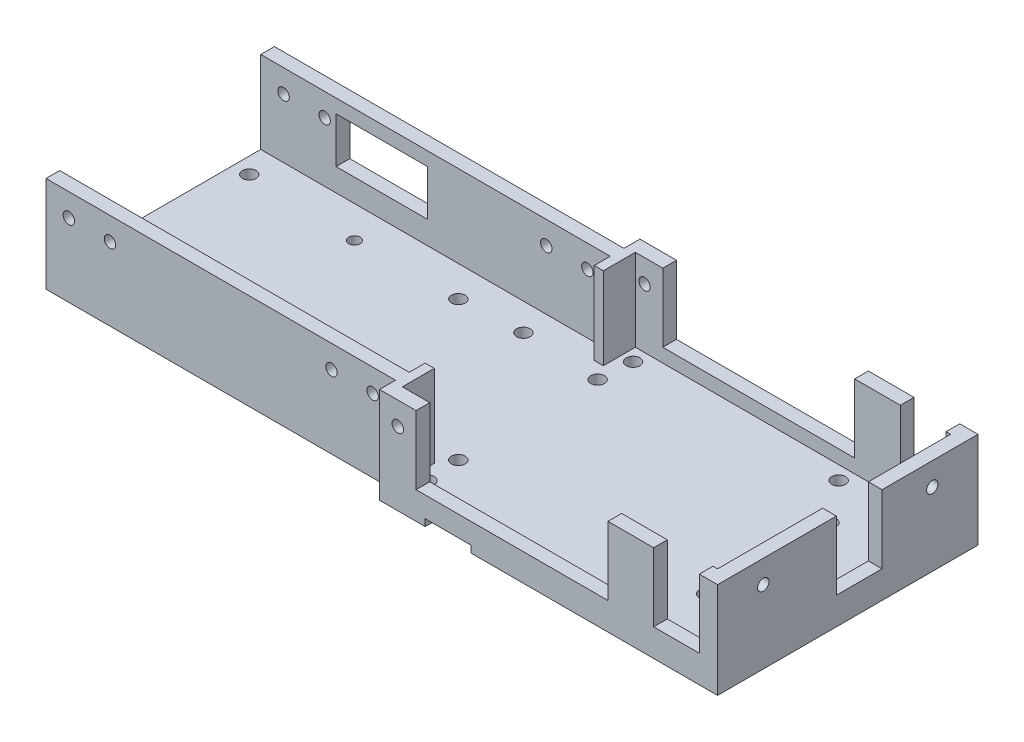
SolidWorks part; units mm, degrees
ref_plane "Front Plane" through (0, 0, 0) normal (0, 0, 1) x (1, 0, 0)
ref_plane "Top Plane" through (0, 0, 0) normal (0, 1, 0) x (1, 0, 0)
ref_plane "Right Plane" through (0, 0, 0) normal (1, 0, 0) x (0, 0, -1)
sketch "Sketch1" plane through (0, 0, 0) normal (0, 1, 0) x (1, 0, 0)
  line L1 (-115.1205, 21.9093) -> (35.3795, 21.9093)
  line L2 (-115.1205, 21.9093) -> (-115.1205, -28.0907)
  line L3 (-115.1205, -28.0907) -> (35.3795, -28.0907)
  line L4 (35.3795, 21.9093) -> (35.3795, -28.0907)
  dimension "D1" = 150.5
  dimension "D2" = 50
extrude "Boss-Extrude1" add sketch "Sketch1" along normal blind 3
sketch "Sketch2" plane through (0, 3, 0) normal (0, 1, 0) x (1, 0, 0)
  line L1 (35.3795, 21.9093) -> (-115.1205, 21.9093) construction
  line L2 (35.3795, -28.0907) -> (35.3795, 21.9093) construction
  line L3 (-115.1205, -28.0907) -> (35.3795, -28.0907) construction
  circle A0 centre (-65.1205, 12.1593) radius 1.5
  circle A1 centre (-65.1205, -18.3407) radius 1.5
  circle A2 centre (-34.6205, -18.3407) radius 1.5
  circle A3 centre (-34.6205, 12.1593) radius 1.5
  circle A6 centre (17.8795, -16.5907) radius 1.5
  circle A7 centre (17.8795, 10.4093) radius 1.5
  circle A8 centre (-111.6205, -19.0907) radius 1.5
  circle A9 centre (-111.6205, 12.9093) radius 1.5
  circle A13 centre (-87.6205, 11.9093) radius 1.25
  circle A14 centre (-87.6205, -18.0907) radius 1.25
  circle A15 centre (-51.6205, 12.9093) radius 1.5
  circle A16 centre (-51.6205, -19.0907) radius 1.5
  dimension "D1" = 3
  dimension "D2" = 3
  dimension "D3" = 3
  dimension "D4" = 3
  dimension "D13" = 17.5
  dimension "D14" = 17.5
  dimension "D19" = 3
  dimension "D20" = 3
  dimension "D25" = 3
  dimension "D26" = 3
  dimension "D37" = 2.5
  dimension "D38" = 2.5
  dimension "D43" = 3
  dimension "D44" = 3
  dimension "D5" = 52.5
  dimension "D6" = 9.75
  dimension "D7" = 52.5
  dimension "D8" = 30.5
  dimension "D9" = 30.5
  dimension "D10" = 30.5
  dimension "D11" = 9.75
  dimension "D12" = 30.5
  dimension "D15" = 17
  dimension "D16" = 17
  dimension "D17" = 22.5
  dimension "D18" = 22.5
  dimension "D23" = 27
  dimension "D24" = 11.5
  dimension "D27" = 32
  dimension "D28" = 9
  dimension "D39" = 30
  dimension "D42" = 10
  dimension "D45" = 60
  dimension "D46" = 60
  dimension "D47" = 32
  dimension "D48" = 9
extrude "Cut-Extrude1" cut sketch "Sketch2" against normal through all
sketch "Sketch4" plane through (0, 3, 0) normal (0, 1, 0) x (1, 0, 0)
  line L0 (35.3795, 21.9093) -> (-115.1205, 21.9093) construction
  line L1 (-38.6205, 25.4093) -> (35.3795, 25.4093)
  line L2 (-38.6205, 25.4093) -> (-38.6205, 21.9093)
  line L3 (-38.6205, 21.9093) -> (35.3795, 21.9093)
  line L4 (35.3795, 25.4093) -> (35.3795, 21.9093)
  line L5 (-38.6205, -28.0907) -> (35.3795, -28.0907)
  line L6 (-38.6205, -28.0907) -> (-38.6205, -31.5907)
  line L7 (-38.6205, -31.5907) -> (35.3795, -31.5907)
  line L8 (35.3795, -28.0907) -> (35.3795, -31.5907)
  line L9 (-115.1205, -28.0907) -> (35.3795, -28.0907) construction
  line L10 (35.3795, -28.0907) -> (35.3795, 21.9093) construction
  point P14 (35.3795, -29.8407)
  line M26 (-115.1205, -28.0907) -> (35.3795, -28.0907)
  dimension "D1" = 74
  dimension "D2" = 3.5
  dimension "D3" = 74
  dimension "D4" = 3.5
  dimension "D5" = 0
  dimension "D6" = 0
  dimension "D7" = 0
  dimension "D8" = 0
extrude "Boss-Extrude2" add sketch "Sketch4" against normal blind 3 contours L8 L6 L7 M26 | L2 L1 L4 L3 region at (-1.6205, 3, 29.8407)
sketch "Sketch5" plane through (0, 3, 0) normal (0, 1, 0) x (1, 0, 0)
  line L0 (-38.6205, -31.5907) -> (35.3795, -31.5907) construction
  line L1 (-38.6205, 25.4093) -> (-38.6205, 21.9093) construction
  line L4 (-38.6205, -28.0907) -> (-38.6205, -31.5907) construction
  line L8 (-38.6205, 25.4093) -> (35.3795, 25.4093) construction
  circle A0 centre (-34.1205, 19.4093) radius 1.5
  circle A1 centre (-34.1205, -25.5907) radius 1.5
  circle A2 centre (10.8795, 19.4093) radius 1.5
  circle A3 centre (10.8795, -25.5907) radius 1.5
  circle A4 centre (-34.6205, 12.1593) radius 1.5 construction
  dimension "D1" = 3
  dimension "D2" = 3
  dimension "D3" = 3
  dimension "D4" = 3
  dimension "D5" = 45
  dimension "D6" = 45
  dimension "D7" = 45
  dimension "D8" = 45
  dimension "D9" = 6
  dimension "D10" = 4.5
  dimension "D11" = 4.5
  dimension "D12" = 6
extrude "Cut-Extrude3" cut sketch "Sketch5" against normal through all
sketch "Sketch6" plane through (0, 3, 0) normal (0, 1, 0) x (1, 0, 0)
  line L0 (31.3795, 25.4093) -> (35.3795, 25.4093)
  line L5 (31.3795, 25.4093) -> (31.3795, 22.4093)
  line L6 (31.3795, 22.4093) -> (35.3795, 22.4093)
  line L7 (35.3795, 25.4093) -> (35.3795, 22.4093)
  line L8 (31.3795, -28.5907) -> (35.3795, -28.5907)
  line L9 (31.3795, -28.5907) -> (31.3795, -31.5907)
  line L10 (31.3795, -31.5907) -> (35.3795, -31.5907)
  line L11 (35.3795, -28.5907) -> (35.3795, -31.5907)
  line L12 (32.3795, 22.4093) -> (35.3795, 22.4093)
  line L13 (32.3795, 22.4093) -> (32.3795, 4.4093)
  line L14 (32.3795, 4.4093) -> (35.3795, 4.4093)
  line L15 (35.3795, 22.4093) -> (35.3795, 4.4093)
  line L16 (32.3795, -5.5907) -> (35.3795, -5.5907)
  line L17 (32.3795, -5.5907) -> (32.3795, -28.5907)
  line L18 (32.3795, -28.5907) -> (35.3795, -28.5907)
  line L19 (35.3795, -5.5907) -> (35.3795, -28.5907)
  line L20 (35.3795, -31.5907) -> (35.3795, 25.4093) construction
  line L21 (-38.6205, 25.4093) -> (35.3795, 25.4093) construction
  line L22 (11.3795, 25.4093) -> (21.3795, 25.4093)
  line L23 (-38.6205, -31.5907) -> (35.3795, -31.5907) construction
  line L24 (-38.6205, 25.4093) -> (-30.6205, 25.4093)
  line L25 (-38.6205, 25.4093) -> (-38.6205, 22.4093)
  line L26 (-38.6205, 22.4093) -> (-30.6205, 22.4093)
  line L27 (-30.6205, 25.4093) -> (-30.6205, 22.4093)
  line L28 (-38.6205, 22.4093) -> (-36.6205, 22.4093)
  line L29 (-38.6205, 22.4093) -> (-38.6205, 15.4093)
  line L30 (-38.6205, 15.4093) -> (-36.6205, 15.4093)
  line L31 (-36.6205, 22.4093) -> (-36.6205, 15.4093)
  line L32 (-38.6205, -21.5907) -> (-36.6205, -21.5907)
  line L33 (-38.6205, -21.5907) -> (-38.6205, -28.5907)
  line L34 (-38.6205, -28.5907) -> (-36.6205, -28.5907)
  line L35 (-36.6205, -21.5907) -> (-36.6205, -28.5907)
  line L36 (-38.6205, -28.5907) -> (-30.6205, -28.5907)
  line L37 (-38.6205, -28.5907) -> (-38.6205, -31.5907)
  line L38 (-38.6205, -31.5907) -> (-30.6205, -31.5907)
  line L39 (-30.6205, -28.5907) -> (-30.6205, -31.5907)
  line L40 (-38.6205, 25.4093) -> (-38.6205, 21.9093) construction
  line L41 (-38.6205, -28.0907) -> (-38.6205, -31.5907) construction
  line L42 (11.3795, 25.4093) -> (11.3795, 22.4093)
  line L43 (11.3795, 22.4093) -> (21.3795, 22.4093)
  line L44 (-38.6205, 21.9093) -> (-115.1205, 21.9093) construction
  line L45 (-115.1205, 21.9093) -> (-38.6205, 21.9093)
  line L46 (-115.1205, 21.9093) -> (-115.1205, 18.9093)
  line L47 (-115.1205, 18.9093) -> (-38.6205, 18.9093)
  line L48 (-38.6205, 21.9093) -> (-38.6205, 18.9093)
  line L49 (-115.1205, -28.0907) -> (-38.6205, -28.0907) construction
  line L50 (-115.1205, -25.0907) -> (-38.6205, -25.0907)
  line L51 (-115.1205, -25.0907) -> (-115.1205, -28.0907)
  line L52 (-115.1205, -28.0907) -> (-38.6205, -28.0907)
  line L53 (-38.6205, -25.0907) -> (-38.6205, -28.0907)
  line L54 (21.3795, 25.4093) -> (21.3795, 22.4093)
  line L55 (11.3795, -28.5907) -> (21.3795, -28.5907)
  line L56 (11.3795, -28.5907) -> (11.3795, -31.5907)
  line L57 (11.3795, -31.5907) -> (21.3795, -31.5907)
  line L58 (21.3795, -28.5907) -> (21.3795, -31.5907)
  line L59 (11.1449, -22.8352) -> (21.1449, -22.8352)
  line L60 (11.1449, -22.8352) -> (11.1449, -25.8352)
  line L61 (11.1449, -25.8352) -> (21.1449, -25.8352)
  line L62 (21.1449, -22.8352) -> (21.1449, -25.8352)
  line L63 (-115.1205, 21.9093) -> (-115.1205, -28.0907) construction
  point P24 (35.3795, 23.9093)
  line M45 (35.3795, -31.5907) -> (35.3795, 25.4093)
  line M46 (35.3795, 25.4093) -> (-38.6205, 25.4093)
  dimension "D13" = 18
  dimension "D20" = 3
  dimension "D1" = 0
  dimension "D2" = 0
  dimension "D3" = 0
  dimension "D4" = 3
  dimension "D5" = 4
  dimension "D6" = 0
  dimension "D7" = 0
  dimension "D8" = 0
  dimension "D9" = 3
  dimension "D10" = 4
  dimension "D11" = 0
  dimension "D12" = 0
  dimension "D14" = 3
  dimension "D15" = 3
  dimension "D16" = 8
  dimension "D17" = 3
  dimension "D18" = 0
  dimension "D19" = 0
  dimension "D21" = 8
  dimension "D22" = 0
  dimension "D23" = 0
  dimension "D24" = 2
  dimension "D25" = 2
  dimension "D26" = 7
  dimension "D27" = 7
  dimension "D28" = 0
  dimension "D29" = 0
  dimension "D30" = 0
  dimension "D31" = 0
  dimension "D32" = 0
  dimension "D33" = 3
  dimension "D34" = 0
  dimension "D35" = 0
  dimension "D36" = 0
  dimension "D37" = 3
  dimension "D38" = 0
  dimension "D39" = 0
  dimension "D40" = 0
  dimension "D41" = 10
  dimension "D42" = 10
  dimension "D43" = 3
  dimension "D44" = 0
  dimension "D45" = 10
  dimension "D46" = 10
  dimension "D47" = 3
extrude "Boss-Extrude3" add sketch "Sketch6" along normal blind 18 contours L5 L6 M45 M46 | L50 L53 L52 L51 | L45 L48 L47 L46 | L24 L27 L26 L25 | L36 L39 L38 L37 | L33 L34 L35 L32 | L31 L30 L29 L28 | L11 L10 L9 L8 | L19 L18 L17 L16 | L15 L14 L13 L12 | L55 L58 L57 L56 | L22 L54 L43 L42 region at (33.3795, 3, -23.9093)
sketch "Sketch8" plane through (0, 3, 0) normal (0, 1, 0) x (1, 0, 0)
  line L0 (21.3795, -28.5907) -> (31.3795, -28.5907)
  line L5 (21.3795, -28.5907) -> (21.3795, -31.5907)
  line L6 (21.3795, -31.5907) -> (31.3795, -31.5907)
  line L7 (31.3795, -28.5907) -> (31.3795, -31.5907)
  line L8 (31.3795, -28.5907) -> (31.3795, -31.5907) construction
  line L9 (21.3795, -31.5907) -> (31.3795, -31.5907) construction
  line L11 (21.3795, -28.5907) -> (21.3795, -31.5907) construction
  line L12 (21.3795, 25.4093) -> (31.3795, 25.4093)
  line L13 (21.3795, 25.4093) -> (21.3795, 23.4093)
  line L14 (21.3795, 23.4093) -> (31.3795, 23.4093)
  line L15 (31.3795, 25.4093) -> (31.3795, 23.4093)
  line L16 (21.3795, 25.4093) -> (31.3795, 25.4093) construction
  line L17 (21.3795, 25.4093) -> (21.3795, 22.4093) construction
  line L18 (31.3795, 25.4093) -> (31.3795, 22.4093) construction
  line L19 (-30.6205, 25.4093) -> (11.3795, 25.4093)
  line L20 (-30.6205, 25.4093) -> (-30.6205, 22.4093)
  line L21 (-30.6205, 22.4093) -> (11.3795, 22.4093)
  line L22 (11.3795, 25.4093) -> (11.3795, 22.4093)
  line L23 (-30.6205, 25.4093) -> (11.3795, 25.4093) construction
  line L24 (11.3795, 25.4093) -> (11.3795, 22.4093) construction
  line L25 (-30.6205, 25.4093) -> (-30.6205, 22.4093) construction
  line L26 (-30.6205, -28.5907) -> (11.3795, -28.5907)
  line L27 (-30.6205, -28.5907) -> (-30.6205, -31.5907)
  line L28 (-30.6205, -31.5907) -> (11.3795, -31.5907)
  line L29 (11.3795, -28.5907) -> (11.3795, -31.5907)
  line L30 (-30.6205, -31.5907) -> (11.3795, -31.5907) construction
  line L31 (-30.6205, -28.5907) -> (-30.6205, -31.5907) construction
  line L32 (11.3795, -28.5907) -> (11.3795, -31.5907) construction
  line L33 (32.3795, 4.4093) -> (35.3795, 4.4093)
  line L34 (32.3795, 4.4093) -> (32.3795, -5.5907)
  line L35 (32.3795, -5.5907) -> (35.3795, -5.5907)
  line L36 (35.3795, 4.4093) -> (35.3795, -5.5907)
  line L38 (35.3795, -5.5907) -> (35.3795, 4.4093) construction
  line L39 (32.3795, 4.4093) -> (35.3795, 4.4093) construction
  line L40 (32.3795, -5.5907) -> (35.3795, -5.5907) construction
  dimension "D1" = 3
  dimension "D2" = 0
  dimension "D3" = 0
  dimension "D4" = 0
  dimension "D5" = 0
  dimension "D6" = 0
  dimension "D7" = 0
  dimension "D8" = 0
  dimension "D9" = 3
  dimension "D10" = 0
  dimension "D11" = 0
  dimension "D12" = 0
  dimension "D13" = 3
  dimension "D14" = 0
  dimension "D15" = 0
  dimension "D16" = 3
  dimension "D17" = 0
  dimension "D18" = 0
  dimension "D19" = 0
extrude "Boss-Extrude4" add sketch "Sketch8" along normal blind 3
sketch "Sketch9" plane through (0, 0, -21.9093) normal (0, 0, -1) x (-1, 0, 0)
  line L0 (38.6205, 0) -> (115.1205, 0) construction
  line L1 (98.6205, 8) -> (78.6205, 8)
  line L2 (98.6205, 8) -> (98.6205, 18)
  line L3 (98.6205, 18) -> (78.6205, 18)
  line L4 (78.6205, 8) -> (78.6205, 18)
  line L6 (38.6205, 0) -> (38.6205, 21) construction
  dimension "D1" = 20
  dimension "D2" = 10
  dimension "D3" = 8
  dimension "D4" = 40
extrude "Cut-Extrude4" cut sketch "Sketch9" against normal up to next
sketch "Sketch10" plane through (35.3795, 0, 0) normal (1, 0, 0) x (0, 0, -1)
  line L0 (-5.5907, 21) -> (-31.5907, 21) construction
  line L1 (-31.5907, 0) -> (-31.5907, 21) construction
  line L2 (25.4093, 0) -> (25.4093, 21) construction
  line L3 (25.4093, 21) -> (4.4093, 21) construction
  circle A0 centre (-21.5907, 16) radius 1.25
  circle A1 centre (15.4093, 16) radius 1.25
  dimension "D1" = 2.5
  dimension "D2" = 2.5
  dimension "D3" = 5
  dimension "D4" = 10
  dimension "D5" = 10
  dimension "D6" = 5
extrude "Cut-Extrude5" cut sketch "Sketch10" against normal up to next
sketch "Sketch11" plane through (0, 0, -21.9093) normal (0, 0, -1) x (-1, 0, 0)
  line L0 (115.1205, 21) -> (38.6205, 21) construction
  line L1 (38.6205, 0) -> (38.6205, 21) construction
  line L2 (115.1205, 21) -> (115.1205, 0) construction
  circle A0 centre (43.6205, 16) radius 1.25
  circle A1 centre (110.1205, 16) radius 1.25
  circle A2 centre (52.6205, 16) radius 1.25
  circle A3 centre (101.1205, 16) radius 1.25
  dimension "D1" = 2.5
  dimension "D2" = 2.5
  dimension "D7" = 2.5
  dimension "D10" = 2.5
  dimension "D3" = 5
  dimension "D4" = 5
  dimension "D5" = 5
  dimension "D6" = 5
  dimension "D8" = 5
  dimension "D9" = 14
  dimension "D11" = 14
  dimension "D12" = 5
extrude "Cut-Extrude6" cut sketch "Sketch11" against normal through all
sketch "Sketch12" plane through (0, 0, -25.4093) normal (0, 0, -1) x (-1, 0, 0)
  line L0 (38.6205, 21) -> (30.6205, 21) construction
  line L2 (38.6205, 0) -> (38.6205, 21) construction
  circle A0 centre (34.6205, 16) radius 1.25
  dimension "D1" = 2.5
  dimension "D2" = 5
  dimension "D3" = 4
extrude "Cut-Extrude7" cut sketch "Sketch12" against normal through all
sketch "Sketch13" plane through (0, 0, 0) normal (0, -1, 0) x (-1, 0, 0)
  line L0 (38.6205, -31.5907) -> (-35.3795, -31.5907) construction
  line L1 (28.6205, -31.5907) -> (18.6205, -31.5907)
  line L2 (28.6205, -31.5907) -> (28.6205, -30.0907)
  line L3 (28.6205, -30.0907) -> (18.6205, -30.0907)
  line L4 (18.6205, -31.5907) -> (18.6205, -30.0907)
  line L5 (28.6205, 25.4093) -> (18.6205, 25.4093)
  line L6 (28.6205, 25.4093) -> (28.6205, 23.9093)
  line L7 (28.6205, 23.9093) -> (18.6205, 23.9093)
  line L8 (18.6205, 25.4093) -> (18.6205, 23.9093)
  line L9 (38.6205, -28.0907) -> (38.6205, -31.5907) construction
  line L10 (38.6205, 25.4093) -> (-35.3795, 25.4093) construction
  line L11 (38.6205, 25.4093) -> (38.6205, 21.9093) construction
  point P14 (28.6205, 24.6593)
  dimension "D1" = 10
  dimension "D2" = 10
  dimension "D3" = 1.5
  dimension "D4" = 1.5
  dimension "D5" = 0
  dimension "D6" = 10
  dimension "D7" = 0
  dimension "D8" = 10
extrude "Cut-Extrude8" cut sketch "Sketch13" against normal blind 1.5
